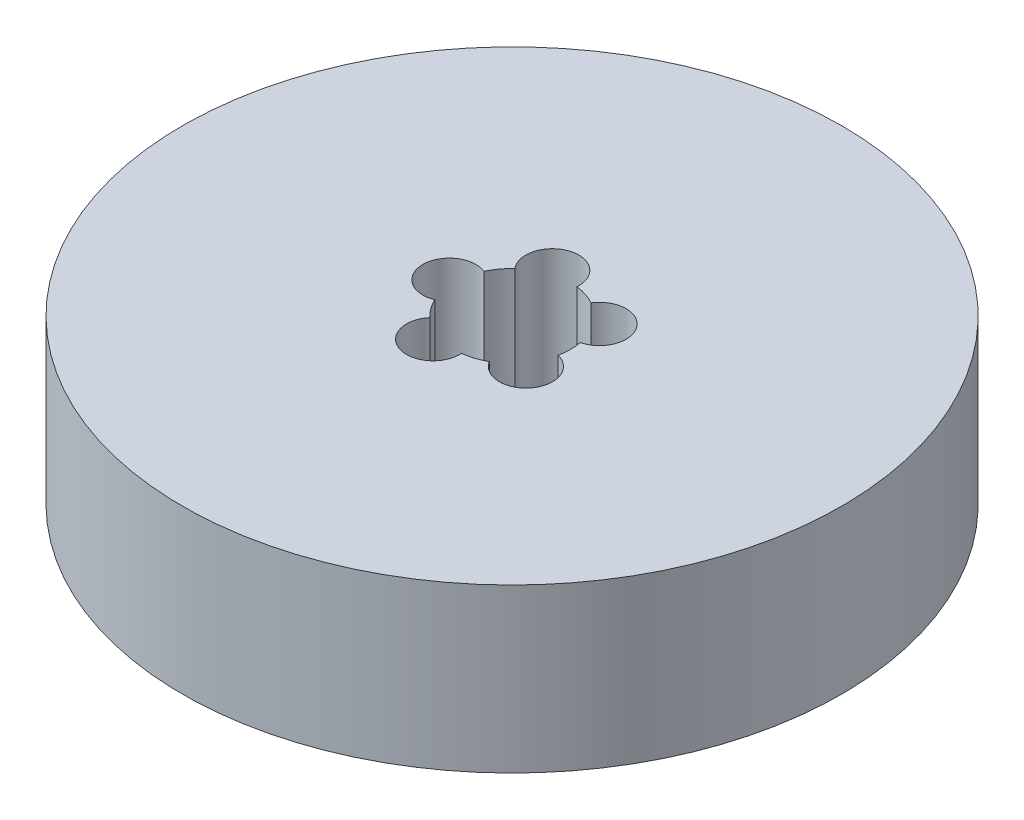
SolidWorks part; units mm, degrees
ref_plane "Front Plane" through (0, 0, 0) normal (0, 0, 1) x (1, 0, 0)
ref_plane "Top Plane" through (0, 0, 0) normal (0, 1, 0) x (1, 0, 0)
ref_plane "Right Plane" through (0, 0, 0) normal (1, 0, 0) x (0, 0, -1)
sketch "Sketch1" plane through (0, 0, 0) normal (0, 1, 0) x (1, 0, 0)
  circle A0 centre (0, 0) radius 42.5
  dimension "FLANGE_OD" = 85
extrude "Boss-Extrude1" add sketch "Sketch1" along normal blind 21
sketch "Sketch2" plane through (0, 0, 0) normal (0, 1, 0) x (1, 0, 0)
  circle A0 centre (0, 0) radius 7.5
  dimension "BORE_D" = 15
extrude "Cut-Extrude1" cut sketch "Sketch2" along normal through all
sketch "Sketch3" plane through (0, 21, 0) normal (0, 1, 0) x (1, 0, 0)
  circle A0 centre (0, 0) radius 8.0808 construction
  circle A1 centre (-8.0808, 0) radius 3.4243
  dimension "BOLT_D" = 6.8486
  dimension "BOLT_PCD" = 16.1615
extrude "Cut-Extrude2" cut sketch "Sketch3" against normal blind 19.5109
pattern_circular "CirPattern1" count 5 over 360 about axis through (0, 0, 0) along (0, 1, 0) of "Cut-Extrude2"
